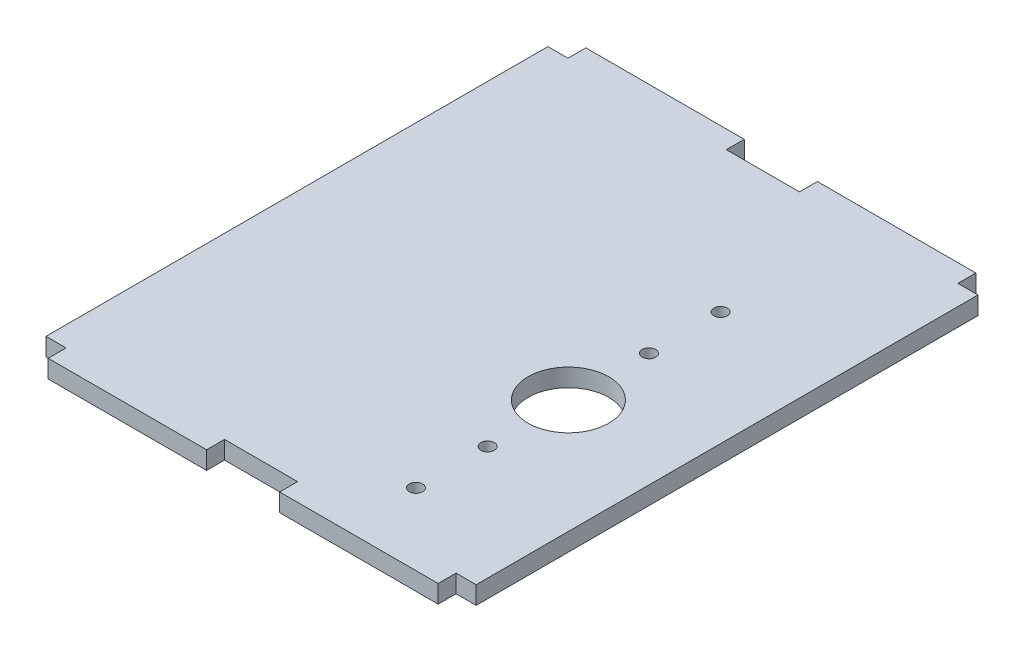
SolidWorks part; units mm, degrees
ref_plane "Front Plane" through (0, 0, 0) normal (0, 0, 1) x (1, 0, 0)
ref_plane "Top Plane" through (0, 0, 0) normal (0, 1, 0) x (1, 0, 0)
ref_plane "Right Plane" through (0, 0, 0) normal (1, 0, 0) x (0, 0, -1)
sketch "Sketch1" plane through (0, 0, 0) normal (0, 1, 0) x (1, 0, 0)
  line L1 (0, 0) -> (304.8, 0)
  line L2 (0, 0) -> (0, 355.6)
  line L3 (0, 355.6) -> (304.8, 355.6)
  line L4 (304.8, 0) -> (304.8, 355.6)
  dimension "D1" = 355.6
  dimension "D2" = 304.8
extrude "Boss-Extrude1" add sketch "Sketch1" along normal blind 12.7
sketch "Sketch2" plane through (0, 0, 0) normal (0, -1, 0) x (1, 0, 0)
  line L0 (0, 0) -> (304.8, 0) construction
  line L1 (0, -355.6) -> (0, 0) construction
  circle A0 centre (224.028, -38.1) radius 4.7625
  circle A1 centre (224.028, -88.9) radius 4.7625
  circle A2 centre (224.028, -203.2) radius 4.7625
  circle A3 centre (224.028, -254) radius 4.7625
  dimension "D3" = 88.9
  dimension "D6" = 9.525
  dimension "D1" = 38.1
  dimension "D2" = 224.028
  dimension "D4" = 203.2
  dimension "D5" = 254
  dimension "D7" = 224.028
  dimension "D8" = 224.028
  dimension "D9" = 224.028
extrude "Cut-Extrude1" cut sketch "Sketch2" against normal blind 12.7
sketch "Sketch3" plane through (0, 12.7, 0) normal (0, 1, 0) x (1, 0, 0)
  line L0 (152.4, 355.6) -> (152.4, 250.206) construction
  line L1 (0, 177.8) -> (22.2548, 177.8) construction
  line L2 (14.224, 355.6) -> (126.492, 355.6)
  line L3 (14.224, 355.6) -> (14.224, 368.3)
  line L4 (0, 355.6) -> (0, 0)
  line L5 (0, 0) -> (304.8, 0)
  line L6 (304.8, 0) -> (304.8, 355.6)
  line L7 (304.8, 355.6) -> (0, 355.6)
  line L8 (0, 355.6) -> (0, 0) construction
  line L9 (0, 0) -> (304.8, 0) construction
  line L10 (304.8, 0) -> (304.8, 355.6) construction
  line L11 (304.8, 355.6) -> (0, 355.6) construction
  line L12 (14.224, 368.3) -> (126.492, 368.3)
  line L13 (126.492, 355.6) -> (126.492, 368.3)
  line L14 (290.576, 368.3) -> (178.308, 368.3)
  line L15 (178.308, 355.6) -> (178.308, 368.3)
  line L16 (290.576, 355.6) -> (178.308, 355.6)
  line L17 (290.576, 355.6) -> (290.576, 368.3)
  line L18 (290.576, 0) -> (290.576, -12.7)
  line L19 (290.576, 0) -> (178.308, 0)
  line L20 (178.308, 0) -> (178.308, -12.7)
  line L21 (290.576, -12.7) -> (178.308, -12.7)
  line L22 (14.224, -12.7) -> (126.492, -12.7)
  line L23 (126.492, 0) -> (126.492, -12.7)
  line L24 (14.224, 0) -> (126.492, 0)
  line L25 (14.224, 0) -> (14.224, -12.7)
  dimension "D2" = 25.908
  dimension "D3" = 112.268
  dimension "D4" = 12.7
  dimension "D1" = 0
extrude "Boss-Extrude2" add sketch "Sketch3" against normal blind 12.7
sketch "Sketch4" plane through (0, 0, 0) normal (0, -1, 0) x (1, 0, 0)
  line L20 (0, 0) -> (0, -355.6)
  line L21 (0, -355.6) -> (14.224, -355.6)
  line L22 (14.224, -355.6) -> (14.224, -368.3)
  line L23 (14.224, -368.3) -> (126.492, -368.3)
  line L24 (126.492, -368.3) -> (126.492, -355.6)
  line L25 (126.492, -355.6) -> (178.308, -355.6)
  line L26 (178.308, -355.6) -> (178.308, -368.3)
  line L27 (178.308, -368.3) -> (290.576, -368.3)
  line L28 (290.576, -368.3) -> (290.576, -355.6)
  line L29 (290.576, -355.6) -> (304.8, -355.6)
  line L30 (304.8, -355.6) -> (304.8, 0)
  line L31 (304.8, 0) -> (290.576, 0)
  line L32 (290.576, 0) -> (290.576, 12.7)
  line L33 (290.576, 12.7) -> (178.308, 12.7)
  line L34 (178.308, 12.7) -> (178.308, 0)
  line L35 (178.308, 0) -> (126.492, 0)
  line L36 (126.492, 0) -> (126.492, 12.7)
  line L37 (126.492, 12.7) -> (14.224, 12.7)
  line L38 (14.224, 12.7) -> (14.224, 0)
  line L39 (14.224, 0) -> (0, 0)
  line L40 (0, 0) -> (0, -355.6)
  line L41 (0, -355.6) -> (14.224, -355.6)
  line L42 (14.224, -355.6) -> (14.224, -368.3)
  line L43 (14.224, -368.3) -> (126.492, -368.3)
  line L44 (126.492, -368.3) -> (126.492, -355.6)
  line L45 (126.492, -355.6) -> (178.308, -355.6)
  line L46 (178.308, -355.6) -> (178.308, -368.3)
  line L47 (178.308, -368.3) -> (290.576, -368.3)
  line L48 (290.576, -368.3) -> (290.576, -355.6)
  line L49 (290.576, -355.6) -> (304.8, -355.6)
  line L50 (304.8, -355.6) -> (304.8, 0)
  line L51 (304.8, 0) -> (290.576, 0)
  line L52 (290.576, 0) -> (290.576, 12.7)
  line L53 (290.576, 12.7) -> (178.308, 12.7)
  line L54 (178.308, 12.7) -> (178.308, 0)
  line L55 (178.308, 0) -> (126.492, 0)
  line L56 (126.492, 0) -> (126.492, 12.7)
  line L57 (126.492, 12.7) -> (14.224, 12.7)
  line L58 (14.224, 12.7) -> (14.224, 0)
  line L59 (14.224, 0) -> (0, 0)
  circle A0 centre (224.1175, -146.05) radius 28.575
  circle A5 centre (224.028, -203.2) radius 4.7625 construction
  circle A6 centre (224.028, -88.9) radius 4.7625 construction
  dimension "D2" = 57.15
  dimension "D3" = 109.5375
  dimension "D4" = 57.15
  dimension "D1" = 0
extrude "Cut-Extrude2" cut sketch "Sketch4" against normal blind 12.7 contours A0
